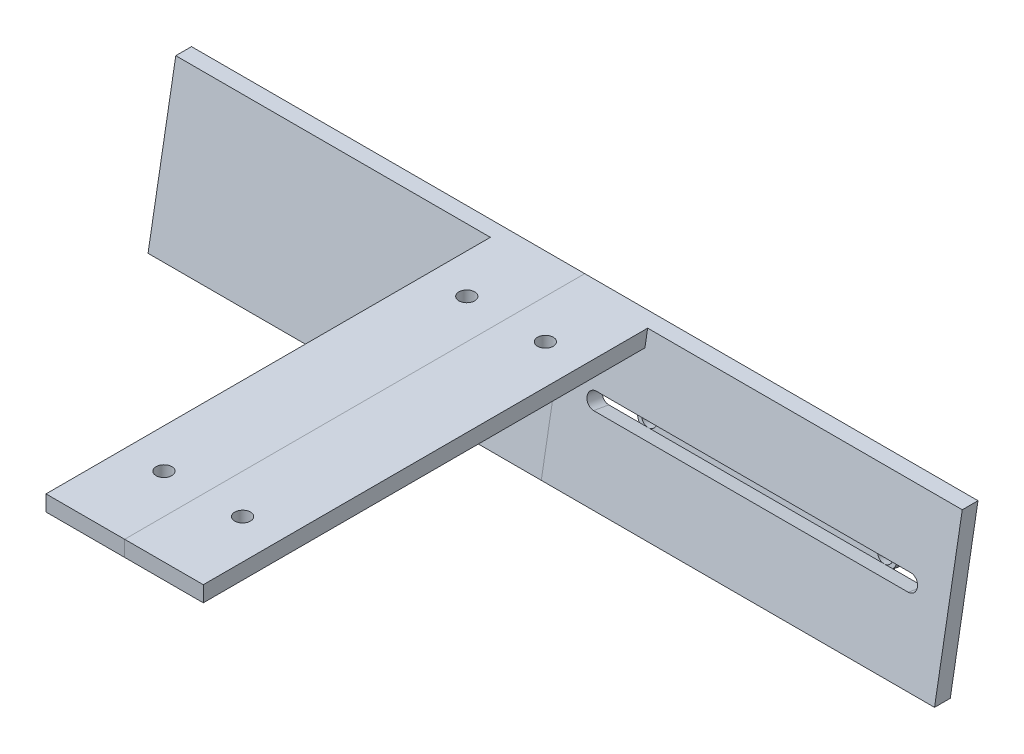
SolidWorks part; units mm, degrees
note: The reader was unsure of these and kept them because the rebuilt part matched: shared geometry of "Sketch1<3>", "Sketch3<3>".
ref_plane "Front Plane" through (0, 0, 0) normal (0, 0, 1) x (1, 0, 0)
ref_plane "Top Plane" through (0, 0, 0) normal (0, 1, 0) x (1, 0, 0)
ref_plane "Right Plane" through (0, 0, 0) normal (1, 0, 0) x (0, 0, -1)
sketch "Sketch1" plane through (0, 0, 0) normal (1, 0, 0) x (0, 0, -1)
  line L0 (0, 0) -> (3.1739, 18)
  line L1 (3.1739, 18) -> (-52.9735, 18)
  line L2 (-52.9735, 18) -> (-52.9735, 20)
  line L3 (-52.9735, 20) -> (5.5265, 20)
  line L4 (5.5265, 20) -> (2, 0)
  line L5 (2, 0) -> (0, 0)
  line L6 (3.1739, 18) -> (3.5265, 20)
  dimension "D1" = 2
  dimension "D2" = 58.5
  dimension "D3" = 80
  dimension "D4" = 20
extrude "Boss-Extrude1" add sketch "Sketch1" along normal blind 10 contours L1 L6 L3 L2
extrude "Boss-Extrude2" add sketch "Sketch1<3>" along normal blind 50 contours L6 L0 L5 L4 L3
sketch "Sketch1<3>" plane through (0, 0, 0) normal (1, 0, 0) x (0, 0, -1) same geometry as "Sketch1"
sketch "Sketch2" plane through (0, 20, 0) normal (0, 1, 0) x (1, 0, 0)
  line L0 (5, -52.9735) -> (5, 5.5265) construction
  line L1 (10, -52.9735) -> (0, -52.9735) construction
  line L2 (50, 5.5265) -> (0, 5.5265) construction
  circle A0 centre (5, -42.9735) radius 1
  circle A1 centre (5, -4.4735) radius 1
  dimension "D1" = 2
  dimension "D2" = 10
  dimension "D3" = 10
extrude "Cut-Extrude1" cut sketch "Sketch2" against normal blind 50
mirror "Mirror1" about plane through (0, 0, 0) normal (1, 0, 0) of bodies 103
sketch "Sketch3" plane through (0, -0.342, -1.9397) normal (0, -0.1736, -0.9848) x (-1, 0, 0)
  line L0 (-25, 4.5016) -> (-25, 0.3473) construction
  line L1 (-40, 16.5016) -> (-10, 16.5016)
  line L2 (-40, 16.5016) -> (-40, 4.5016)
  line L3 (-40, 4.5016) -> (-10, 4.5016)
  line L4 (-10, 16.5016) -> (-10, 4.5016)
  line L5 (-50, 0.3473) -> (0, 0.3473) construction
  line L6 (-40, 10.5016) -> (-50, 10.5016) construction
  line L7 (-50, 20.6558) -> (-50, 0.3473) construction
  line L8 (-45, 10.5016) -> (-5, 10.5016) construction
  line L9 (-45, 11.5016) -> (-5, 11.5016)
  line L10 (-45, 9.5016) -> (-5, 9.5016)
  line L11 (0, 20.6558) -> (0, 0.3473) construction
  circle A0 centre (-40, 10.5016) radius 1
  circle A1 centre (-10, 10.5016) radius 1
  circle A2 centre (-40, 10.5016) radius 1.5
  circle A3 centre (-10, 10.5016) radius 1.5
  arc A4 (-45, 11.5016) -> (-45, 9.5016) centre (-45, 10.5016) ccw
  arc A5 (-5, 9.5016) -> (-5, 11.5016) centre (-5, 10.5016) ccw
  point P21 (-25, 10.5016)
  dimension "D1" = 2
  dimension "D5" = 1
  dimension "D7" = 5
  dimension "D2" = 12
  dimension "D3" = 30
  dimension "D6" = 5
  dimension "D4" = 0.5
extrude "Cut-Extrude2" cut sketch "Sketch3" against normal blind 2 contours L9 A4 L10 A2 | L9 A2 L10 A0 | L2 A0 | L2 A0 | L10 A2 L9 A0 | A3 L9 A2 L10 | L9 A3 L10 A1 | L4 A1 | L4 A1 | L10 A3 L9 A1 | L10 A5 L9 A3
extrude "Boss-Extrude3" add sketch "Sketch3<3>" along normal blind 1.5 separate body contours A3 L4 L1 L2 A2 L3 | L2 A2 A0 | L2 A2 A0 | L4 A3 A1 | L4 A3 A1 | A3 L4 L1 L2 A2 L9 | A3 L10 A2 L2 L3 L4 | L2 A2 L10 | L10 A2 L2 | L2 A2 L9 | L9 A2 L2 | L10 A3 L4 | L4 A3 L10 | L9 A3 L4 | L4 A3 L9
sketch "Sketch3<3>" plane through (0, -0.342, -1.9397) normal (0, -0.1736, -0.9848) x (-1, 0, 0) same geometry as "Sketch3"
sketch "Sketch4" plane through (0, -0.6025, -3.4169) normal (0, -0.1736, -0.9848) x (-1, 0, 0)
  text T0 "SENSOR\r\n"
  point P1 (-41.0773, 2.3132)
  point P2 (0, 0)
  point P3 (-33.1245, 7.6657)
extrude "Cut-Extrude3" cut sketch "Sketch4" against normal blind 0.2
